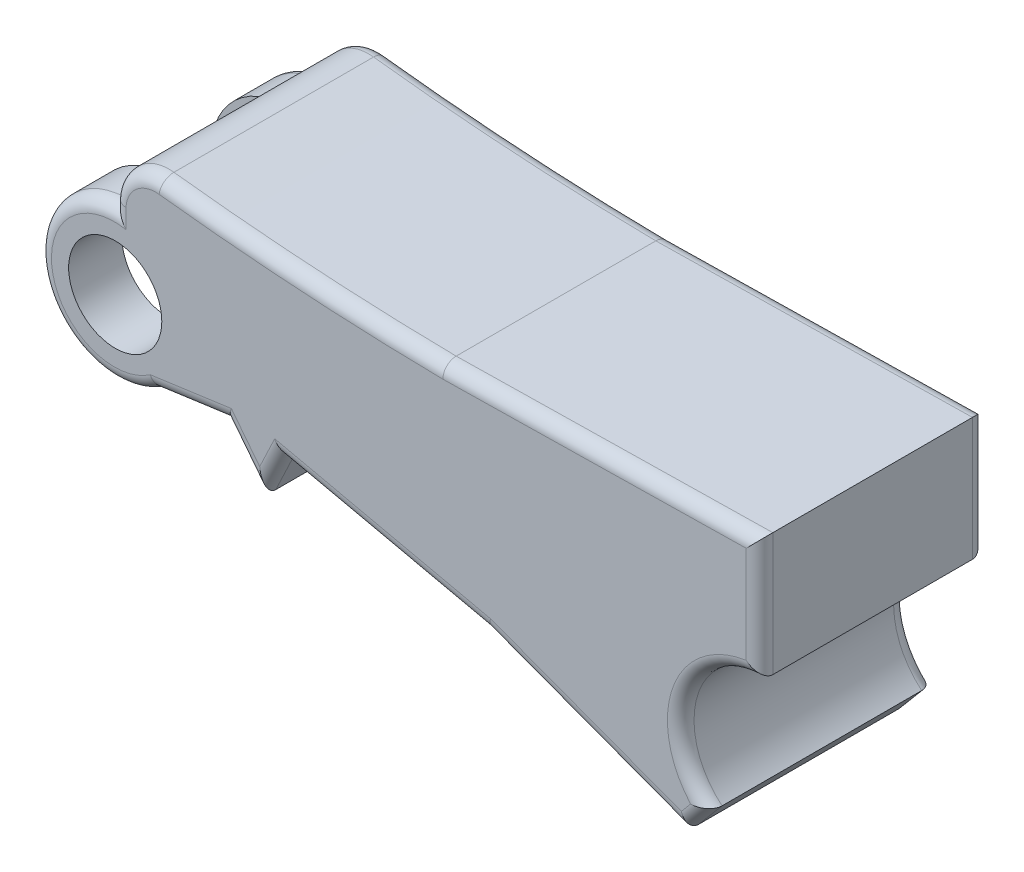
SolidWorks part; units mm, degrees
ref_plane "Front Plane" through (0, 0, 0) normal (0, 0, 1) x (1, 0, 0)
ref_plane "Top Plane" through (0, 0, 0) normal (0, 1, 0) x (1, 0, 0)
ref_plane "Right Plane" through (0, 0, 0) normal (1, 0, 0) x (0, 0, -1)
sketch "Sketch1" plane through (0, 0, 0) normal (0, 0, 1) x (1, 0, 0)
  line L0 (-15.7119, -11.275) -> (-12.9457, -14.8145)
  line L1 (43.4715, 79.5718) -> (338.8048, 79.5718) construction
  line L2 (0.6076, 0.6499) -> (24.4018, 1.0609)
  line L3 (24.4018, 1.0609) -> (24.4018, -8.1766)
  line L4 (20.584, -18.6253) -> (18.8396, -20.6937)
  line L5 (18.8396, -20.6937) -> (3.9062, -15.1089)
  line L6 (3.9062, -15.1089) -> (-11.4655, -11.693)
  line L7 (-24.2, -1.0583) -> (-24.2, -1.4475)
  line L10 (-21.0105, -12.0106) -> (-15.7119, -11.275)
  line L12 (-12.9457, -14.8145) -> (-11.4655, -11.693)
  arc A0 (-24.2, -1.0583) -> (-20.5982, 2.0087) centre (-20.9682, -1.2052) cw
  arc A1 (-20.5982, 2.0087) -> (0.6076, 0.6499) centre (3.4175, 210.6497) ccw
  arc A2 (24.4018, -8.1766) -> (20.584, -18.6253) centre (24.4018, -14.0984) ccw
  arc A5 (-24.2, -1.4475) -> (-21.0105, -12.0106) centre (-24.073, -7.1722) ccw
  point P2 (-27.3993, -8.1766)
  point P4 (0, 0)
  dimension "D1" = 45
extrude "Boss-Extrude1" add sketch "Sketch1" along normal mid plane 17 contours L10 L12 L6 L5 L4 A2 L3 L2 A1 A0 L7 | L12 L6 L5 L4 A2 L3 L2 A1 A0 L7 A5 L10 L0 region at (-0.8619, -6.8854, 0)
sketch "Sketch2" plane through (0, 0, 0) normal (0, 0, 1) x (1, 0, 0)
  circle A0 centre (-24.7242, -7.7891) radius 9
  point P2 (-27.7842, -8.4811)
  point P3 (-20.963, -8.6877)
  point P4 (-27.4799, -8.6979)
  point P6 (-24.7242, -7.7891)
  dimension "D1" = 18
extrude "Cut-Extrude1" cut sketch "Sketch2" against normal mid plane 9
sketch "Sketch3" plane through (0, 0, 8.5) normal (0, 0, 1) x (1, 0, 0)
  circle A0 centre (-24.0093, -7.1527) radius 3.5
  point P3 (-28.5248, -8.8514)
  point P4 (-28.0063, -8.8514)
  point P5 (-21.1855, -8.6629)
  point P6 (-27.6801, -8.0973)
  point P7 (-24.0093, -7.1527)
  dimension "D1" = 7
extrude "Cut-Extrude2" cut sketch "Sketch3" against normal through all
fillet "Fillet1" radius 1 27 edges at (-24.2, -1.2529, 8.5) (-23.0656, 1.2579, 8.5) (-10.0125, 1.0609, 8.5) (12.5047, 0.8554, 8.5) (24.4018, -3.5578, 8.5) (18.8396, -12.0661, 8.5) (11.3729, -17.9013, 8.5) (-3.7797, -13.4009, 8.5) (-12.2056, -13.2537, 8.5) (-18.3612, -11.6428, 8.5) (-18.3612, -11.6428, -8.5) (-12.2056, -13.2537, -8.5) (-3.7797, -13.4009, -8.5) (11.3729, -17.9013, -8.5) (18.8396, -12.0661, -8.5) (24.4018, -3.5578, -8.5) (12.5047, 0.8554, -8.5) (-10.0125, 1.0609, -8.5) (-23.0656, 1.2579, -8.5) (-24.2, -1.2529, -8.5) (-20.5093, -7.1527, -8.5) (19.7118, -19.6595, 8.5) (19.7118, -19.6595, -8.5) (-29.5546, -8.8274, 8.5) (-29.5546, -8.8274, -8.5) (-14.3288, -13.0447, 8.5) (-14.3288, -13.0447, -8.5)
